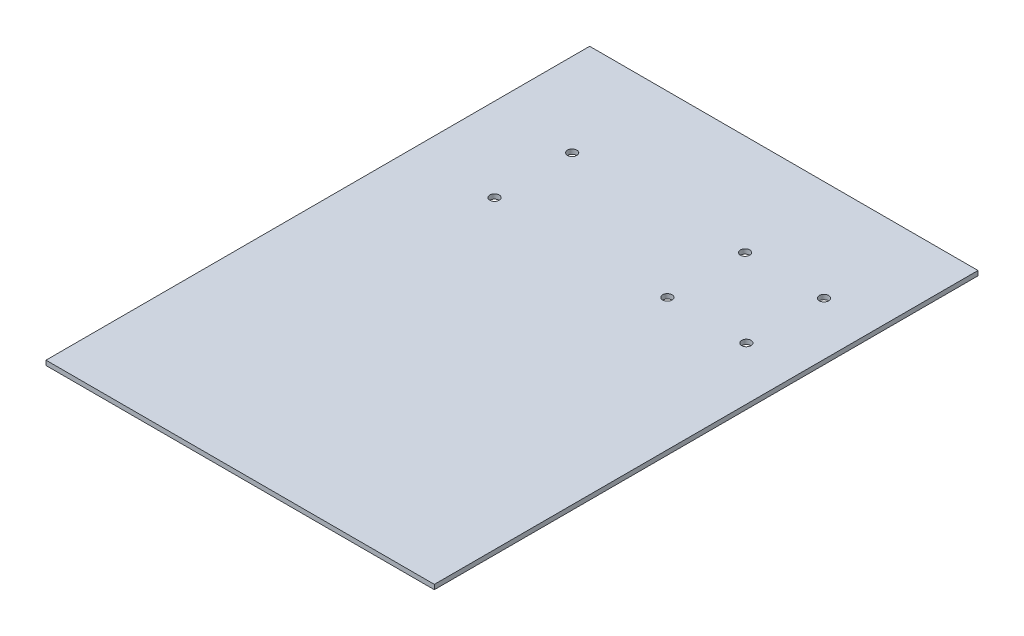
SolidWorks part; units mm, degrees
ref_plane "Front Plane" through (0, 0, 0) normal (0, 0, 1) x (1, 0, 0)
ref_plane "Top Plane" through (0, 0, 0) normal (0, 1, 0) x (1, 0, 0)
ref_plane "Right Plane" through (0, 0, 0) normal (1, 0, 0) x (0, 0, -1)
sketch "Sketch2" plane through (0, 0, 0) normal (0, 1, 0) x (1, 0, 0)
  line L1 (0, 0) -> (250, 0)
  line L2 (0, 0) -> (0, 350)
  line L3 (0, 350) -> (250, 350)
  line L4 (250, 0) -> (250, 350)
  dimension "D1" = 350
  dimension "D2" = 250
extrude "Boss-Extrude1" add sketch "Sketch2" along normal blind 3
hole_wizard "Ø6.0mm Dowel Hole1" positions "Sketch7" profile "Sketch8" hole size "Ø6.0" standard "ANSI Metric" end condition up to next
sketch "Sketch7" plane through (0, 3, 0) normal (0, 1, 0) x (1, 0, 0)
  point P0 (53.7446, 235)
  point P3 (53.7446, 285)
  point P6 (165.0308, 285)
  point P9 (165.0308, 235)
  point P12 (215.8608, 235)
  point P15 (215.8608, 285)
  point P18 (0, 0)
  point P19 (0, 0)
  point P20 (0, 0)
  point P21 (0, 0)
  point P22 (0, 0)
  point P23 (0, 0)
  point P24 (0, 0)
sketch "Sketch8" plane through (53.7446, 3, -235) normal (1, 0, 0) x (0, 0, 1)
  line L0 (0, 0) -> (0, 3)
  line L1 (0, 3) -> (3, 3)
  line L2 (3, 3) -> (3, 0)
  line L5 (3, 0) -> (0, 0)
  line L11 (0, -6.35) -> (0, 107.95) construction
  dimension "Thru Hole Dia." = 6
  dimension "Thru Hole Depth" = 3
